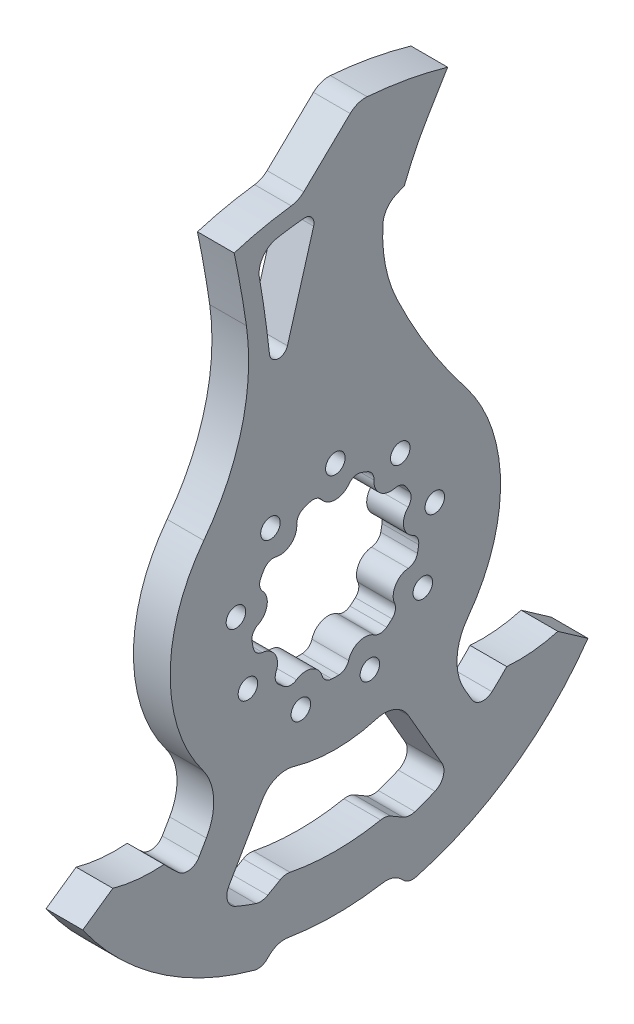
SolidWorks part; units mm, degrees
material "AR500"
ref_plane "Front Plane" through (0, 0, 0) normal (0, 0, 1) x (1, 0, 0)
ref_plane "Top Plane" through (0, 0, 0) normal (0, 1, 0) x (1, 0, 0)
ref_plane "Right Plane" through (0, 0, 0) normal (1, 0, 0) x (0, 0, -1)
other "Center of Mass"
sketch "Sketch1" plane through (0, 0, 0) normal (1, 0, 0) x (0, 0, -1)
  circle A0 centre (0, 0) radius 139.7 construction
  circle A1 centre (0, 0) radius 106.68 construction
  circle A2 centre (0, 0) radius 44.45 construction
  dimension "D1" = 279.4
  dimension "D2" = 33.02
  dimension "D3" = 88.9
sketch "Sketch2" plane through (0, 0, 0) normal (1, 0, 0) x (0, 0, -1)
  line L0 (0, 0) -> (38.858, 134.187) construction
  line L1 (38.858, 134.187) -> (32.2885, 123.3181)
  line L2 (0, 0) -> (0, 61.679) construction
  line L3 (7.5549, 139.4956) -> (-12.768, 119.9725)
  line L4 (-35.0051, 115.4602) -> (-40.3483, 140.8902) construction
  line L5 (23.88, 106.192) -> (20.1469, 96.5425) construction
  line L6 (23.88, 106.192) -> (16.9106, 103.1109)
  line L7 (16.9106, 103.1109) -> (16.6566, 100.7528)
  line L8 (-35.0051, 115.4602) -> (-4.6687, 124.6576) construction
  line L10 (0, -100.33) -> (0, 0) construction
  line L11 (-20.0866, -98.2987) -> (-25.4, -103.6121)
  line L16 (-49.9001, -64.1593) -> (-37.6706, -42.9773)
  line L17 (87.3871, -61.1891) -> (76.9839, -53.9047)
  line L18 (-87.3871, -61.1891) -> (-76.9839, -53.9047)
  line L19 (49.9001, -64.1593) -> (37.6706, -42.9773)
  line L24 (53.8815, -53.8815) -> (0, 0) construction
  line L25 (20.0866, -98.2987) -> (25.4, -103.6121)
  circle A0 centre (0, 0) radius 139.7 construction
  arc A1 (38.858, 134.187) -> (7.5549, 139.4956) centre (0, 0) ccw
  arc A2 (-12.768, 119.9725) -> (-35.0051, 115.4602) centre (0, 0) ccw
  arc A3 (32.2885, 123.3181) -> (23.88, 106.192) centre (125.9607, 66.6999) ccw
  arc A4 (44.9569, 35.2845) -> (37.6706, -42.9773) centre (0, 0) cw
  circle A5 centre (0, 0) radius 44.45 construction
  arc A6 (21.2843, 73.5004) -> (16.6566, 100.7528) centre (67.1642, 95.3105) cw
  arc A7 (-35.0051, 115.4602) -> (-30.7712, 91.5455) centre (-407.8633, 37.1165) cw
  arc A8 (-30.7712, 91.5455) -> (-45.5098, 34.5685) centre (-106.1896, 80.6597) cw
  arc A9 (-45.5098, 34.5685) -> (-37.6706, -42.9773) centre (0, 0) ccw
  arc A10 (-87.3871, -61.1891) -> (-25.4, -103.6121) centre (0, 0) ccw
  circle A11 centre (0, 0) radius 106.68 construction
  arc A18 (-76.9839, -53.9047) -> (-59.2852, -55.6031) centre (-63.357, -4.9665) ccw
  arc A19 (-59.2852, -55.6031) -> (-49.9001, -64.1593) centre (0, 0) ccw
  arc A20 (-20.0866, -98.2987) -> (20.0866, -98.2987) centre (0, 0) ccw
  arc A21 (59.2852, -55.6031) -> (49.9001, -64.1593) centre (0, 0) cw
  arc A22 (76.9839, -53.9047) -> (59.2852, -55.6031) centre (63.357, -4.9665) cw
  arc A23 (87.3871, -61.1891) -> (25.4, -103.6121) centre (0, 0) cw
  circle A24 centre (0, 0) radius 44.45
  arc A25 (21.2843, 73.5004) -> (44.9569, 35.2845) centre (204.8038, 160.7405) ccw
  dimension "D4" = 19.05
  dimension "D11" = 57.15
  dimension "D13" = 50.8
  dimension "D14" = 381
  dimension "D16" = 76.2
  dimension "D19" = 6.35
  dimension "D21" = 55
  dimension "D26" = 17.78
  dimension "D22" = 25.4
  dimension "D23" = 50.8
  dimension "D27" = 12.7
  dimension "D29" = 203.2
  dimension "D1" = 15
  dimension "D2" = 16.15
  dimension "D3" = 15
  dimension "D5" = 31.75
  dimension "D6" = 12.7
  dimension "D7" = 31.75
  dimension "D8" = 5
  dimension "D9" = 45
  dimension "D10" = 10
  dimension "D12" = 7.62
  dimension "D15" = 85
  dimension "D17" = 76.2
  dimension "D18" = 25.4
  dimension "D20" = 45
  dimension "D24" = 12.7
  dimension "D25" = 45
  dimension "D28" = 30
extrude "Boss-Extrude1" add sketch "Sketch2" along normal mid plane 12.7
sketch "Sketch3" plane through (6.35, 0, 0) normal (1, 0, 0) x (0, 0, -1)
  line L1 (-7.513, 109.7387) -> (-16.5762, 78.441)
  line L2 (16.6566, 100.7528) -> (16.9106, 103.1109) construction
  line L3 (-3.2803, 66.3447) -> (4.4504, 105.5668) construction
  line L4 (16.9106, 103.1109) -> (-8.0099, 108.0227) construction
  arc A0 (-12.768, 119.9725) -> (-35.0051, 115.4602) centre (0, 0) ccw construction
  arc A1 (-30.7712, 91.5455) -> (-35.0051, 115.4602) centre (-407.8633, 37.1165) ccw construction
  arc A2 (-7.513, 109.7387) -> (-10.8645, 113.7825) centre (-10.5627, 110.6219) ccw
  arc A3 (-12.768, 119.9725) -> (-35.0051, 115.4602) centre (0, 0) ccw construction
  arc A4 (-30.7712, 91.5455) -> (-35.0051, 115.4602) centre (-407.8633, 37.1165) ccw construction
  arc A5 (-10.8645, 113.7825) -> (-27.6085, 110.9156) centre (0, 0) ccw
  arc A6 (-22.7823, 78.981) -> (-27.6085, 110.9156) centre (-407.8633, 37.1165) ccw
  arc A7 (-24.4863, 92.4527) -> (-27.6085, 110.9156) centre (-407.8633, 37.1165) ccw construction
  arc A8 (-12.096, 113.6582) -> (-27.6085, 110.9156) centre (0, 0) ccw construction
  arc A14 (-22.7823, 78.981) -> (-16.5762, 78.441) centre (-19.6259, 79.3242) ccw
  point P18 (16.9106, 103.1109)
  dimension "D5" = 3.175
  dimension "D7" = 3.175
  dimension "D3" = 10
  dimension "D4" = 25.4
  dimension "D1" = 6.35
extrude "Cut-Extrude1" cut sketch "Sketch3" against normal through all
fillet "Fillet1" radius 7.62 6 edges at (0, 103.1109, -16.9106) (0, 110.9156, 27.6085) (0, 139.4956, -7.5549) (0, 119.9725, 12.768) (0, -98.2987, -20.0866) (0, -98.2987, 20.0866)
fillet "Fillet4" radius 19.05 2 edges at (0, -42.9773, -37.6706) (0, -42.9773, 37.6706)
fillet "Fillet2" radius 4.572 4 edges at (0, -103.6121, 25.4) (0, -103.6121, -25.4) (0, -64.1593, -49.9001) (0, -64.1593, 49.9001)
sketch "Sketch4" plane through (6.35, 0, 0) normal (1, 0, 0) x (0, 0, -1)
  line L0 (-21.1843, -46.1721) -> (-39.646, -78.1487)
  line L1 (-44.6265, -55.0252) -> (-47.1846, -59.4559) construction
  line L2 (0, -81.28) -> (0, -50.8)
  line L3 (-25.3274, -83.8901) -> (-17.5035, -79.373)
  line L4 (-11.6185, -94.3061) -> (-25.8749, -102.5371) construction
  arc A0 (-39.646, -78.1487) -> (-25.3274, -83.8901) centre (0, 0) ccw
  arc A1 (0, -50.8) -> (-21.1843, -46.1721) centre (0, 0) cw
  circle A2 centre (0, 0) radius 44.45 construction
  circle A3 centre (0, 0) radius 106.68 construction
  arc A4 (-17.5035, -79.373) -> (0, -81.28) centre (0, 0) ccw
  arc A5 (-16.2916, -98.9984) -> (16.2916, -98.9984) centre (0, 0) ccw construction
  arc A6 (-87.3871, -61.1891) -> (-27.9851, -102.9439) centre (0, 0) ccw construction
  arc A7 (-16.2916, -98.9984) -> (-22.9171, -101.1292) centre (-17.5289, -106.5173) ccw construction
  dimension "D1" = 50.8
  dimension "D3" = 19.05
  dimension "D4" = 19.05
  dimension "D2" = 15.875
  dimension "D5" = 30
  dimension "D6" = 15.875
extrude "Cut-Extrude2" cut sketch "Sketch4" against normal through all
mirror "Mirror1" about plane through (-6.35, -81.28, 0) normal (0, 0, -1) of "Cut-Extrude2"
fillet "Fillet3" radius 5.08 6 edges at (0, -78.1487, -39.646) (0, -83.8901, -25.3274) (0, -79.373, -17.5035) (0, -79.373, 17.5035) (0, -83.8901, 25.3274) (0, -78.1487, 39.646)
fillet "Fillet5" radius 9.525 2 edges at (0, -46.1721, -21.1843) (0, -46.1721, 21.1843)
ref_axis "Axis1" through (6.35, 0, 0) along (-1, 0, 0)
sketch "Sketch5" plane through (-6.35, 0, 0) normal (-1, 0, 0) x (0, 0, 1)
  arc A36 (-24.1266, 15.3113) -> (-25.3233, 13.2386) centre (0, 0) ccw construction
  arc A37 (-20.6919, 16.6942) -> (-24.1266, 15.3113) centre (-21.4459, 13.6101) ccw construction
  arc A38 (-20.6919, 16.6942) -> (-12.8475, 23.2765) centre (-19.184, 22.8626) ccw construction
  arc A39 (-10.8892, 26.4189) -> (-12.8475, 23.2765) centre (-9.6793, 23.4834) ccw construction
  arc A40 (-8.6401, 27.2374) -> (-10.8892, 26.4189) centre (0, 0) ccw construction
  arc A41 (-5.1201, 26.089) -> (-8.6401, 27.2374) centre (-7.6801, 24.2111) ccw construction
  arc A42 (-5.1201, 26.089) -> (5.1201, 26.089) centre (0, 29.845) ccw construction
  arc A43 (8.6401, 27.2374) -> (5.1201, 26.089) centre (7.6801, 24.2111) ccw construction
  arc A44 (10.8892, 26.4189) -> (8.6401, 27.2374) centre (0, 0) ccw construction
  arc A45 (12.8475, 23.2765) -> (10.8892, 26.4189) centre (9.6793, 23.4834) ccw construction
  arc A46 (12.8475, 23.2765) -> (20.6919, 16.6942) centre (19.184, 22.8626) ccw construction
  arc A47 (24.1266, 15.3113) -> (20.6919, 16.6942) centre (21.4459, 13.6101) ccw construction
  arc A48 (25.3233, 13.2386) -> (24.1266, 15.3113) centre (0, 0) ccw construction
  arc A49 (24.8036, 9.5726) -> (25.3233, 13.2386) centre (22.5096, 11.7677) ccw construction
  arc A50 (24.8036, 9.5726) -> (26.5818, -0.512) centre (29.3916, 5.1825) ccw construction
  arc A51 (28.324, -3.7791) -> (26.5818, -0.512) centre (25.1769, -3.3592) ccw construction
  arc A52 (27.9084, -6.1361) -> (28.324, -3.7791) centre (0, 0) ccw construction
  arc A53 (25.1538, -8.6104) -> (27.9084, -6.1361) centre (24.8075, -5.4543) ccw construction
  arc A54 (25.1538, -8.6104) -> (20.0337, -17.4786) centre (25.8465, -14.9225) ccw construction
  arc A55 (19.2682, -21.1013) -> (20.0337, -17.4786) centre (17.1273, -18.7567) ccw construction
  arc A56 (17.4348, -22.6397) -> (19.2682, -21.1013) centre (0, 0) ccw construction
  arc A57 (13.7343, -22.7645) -> (17.4348, -22.6397) centre (15.4976, -20.1242) ccw construction
  arc A58 (13.7343, -22.7645) -> (4.1117, -26.2669) centre (10.2076, -28.0451) ccw construction
  arc A59 (1.1967, -28.5499) -> (4.1117, -26.2669) centre (1.0637, -25.3777) ccw construction
  arc A60 (-1.1967, -28.5499) -> (1.1967, -28.5499) centre (0, 0) ccw construction
  arc A61 (-4.1117, -26.2669) -> (-1.1967, -28.5499) centre (-1.0637, -25.3777) ccw construction
  arc A62 (-4.1117, -26.2669) -> (-13.7343, -22.7645) centre (-10.2076, -28.0451) ccw construction
  arc A63 (-17.4348, -22.6397) -> (-13.7343, -22.7645) centre (-15.4976, -20.1242) ccw construction
  arc A64 (-19.2682, -21.1013) -> (-17.4348, -22.6397) centre (0, 0) ccw construction
  arc A65 (-20.0337, -17.4786) -> (-19.2682, -21.1013) centre (-17.1273, -18.7567) ccw construction
  arc A66 (-20.0337, -17.4786) -> (-25.1538, -8.6104) centre (-25.8465, -14.9225) ccw construction
  arc A67 (-27.9084, -6.1361) -> (-25.1538, -8.6104) centre (-24.8075, -5.4543) ccw construction
  arc A68 (-28.324, -3.7791) -> (-27.9084, -6.1361) centre (0, 0) ccw construction
  arc A69 (-26.5818, -0.512) -> (-28.324, -3.7791) centre (-25.1769, -3.3592) ccw construction
  arc A70 (-26.5818, -0.512) -> (-24.8036, 9.5726) centre (-29.3916, 5.1825) ccw construction
  arc A71 (-25.3233, 13.2386) -> (-24.8036, 9.5726) centre (-22.5096, 11.7677) ccw construction
  circle A108 centre (0, 0) radius 44.45 construction
  circle A109 centre (0, 0) radius 44.45
  arc A146 (-24.1266, 15.3113) -> (-25.3233, 13.2386) centre (0, 0) ccw construction
  arc A147 (-20.6919, 16.6942) -> (-24.1266, 15.3113) centre (-21.4459, 13.6101) ccw construction
  arc A148 (-20.6919, 16.6942) -> (-12.8475, 23.2765) centre (-19.184, 22.8626) ccw construction
  arc A149 (-10.8892, 26.4189) -> (-12.8475, 23.2765) centre (-9.6793, 23.4834) ccw construction
  arc A150 (-8.6401, 27.2374) -> (-10.8892, 26.4189) centre (0, 0) ccw construction
  arc A151 (-5.1201, 26.089) -> (-8.6401, 27.2374) centre (-7.6801, 24.2111) ccw construction
  arc A152 (-5.1201, 26.089) -> (5.1201, 26.089) centre (0, 29.845) ccw construction
  arc A153 (8.6401, 27.2374) -> (5.1201, 26.089) centre (7.6801, 24.2111) ccw construction
  arc A154 (10.8892, 26.4189) -> (8.6401, 27.2374) centre (0, 0) ccw construction
  arc A155 (12.8475, 23.2765) -> (10.8892, 26.4189) centre (9.6793, 23.4834) ccw construction
  arc A156 (12.8475, 23.2765) -> (20.6919, 16.6942) centre (19.184, 22.8626) ccw construction
  arc A157 (24.1266, 15.3113) -> (20.6919, 16.6942) centre (21.4459, 13.6101) ccw construction
  arc A158 (25.3233, 13.2386) -> (24.1266, 15.3113) centre (0, 0) ccw construction
  arc A159 (24.8036, 9.5726) -> (25.3233, 13.2386) centre (22.5096, 11.7677) ccw construction
  arc A160 (24.8036, 9.5726) -> (26.5818, -0.512) centre (29.3916, 5.1825) ccw construction
  arc A161 (28.324, -3.7791) -> (26.5818, -0.512) centre (25.1769, -3.3592) ccw construction
  arc A162 (27.9084, -6.1361) -> (28.324, -3.7791) centre (0, 0) ccw construction
  arc A163 (25.1538, -8.6104) -> (27.9084, -6.1361) centre (24.8075, -5.4543) ccw construction
  arc A164 (25.1538, -8.6104) -> (20.0337, -17.4786) centre (25.8465, -14.9225) ccw construction
  arc A165 (19.2682, -21.1013) -> (20.0337, -17.4786) centre (17.1273, -18.7567) ccw construction
  arc A166 (17.4348, -22.6397) -> (19.2682, -21.1013) centre (0, 0) ccw construction
  arc A167 (13.7343, -22.7645) -> (17.4348, -22.6397) centre (15.4976, -20.1242) ccw construction
  arc A168 (13.7343, -22.7645) -> (4.1117, -26.2669) centre (10.2076, -28.0451) ccw construction
  arc A169 (1.1967, -28.5499) -> (4.1117, -26.2669) centre (1.0637, -25.3777) ccw construction
  arc A170 (-1.1967, -28.5499) -> (1.1967, -28.5499) centre (0, 0) ccw construction
  arc A171 (-4.1117, -26.2669) -> (-1.1967, -28.5499) centre (-1.0637, -25.3777) ccw construction
  arc A172 (-4.1117, -26.2669) -> (-13.7343, -22.7645) centre (-10.2076, -28.0451) ccw construction
  arc A173 (-17.4348, -22.6397) -> (-13.7343, -22.7645) centre (-15.4976, -20.1242) ccw construction
  arc A174 (-19.2682, -21.1013) -> (-17.4348, -22.6397) centre (0, 0) ccw construction
  arc A175 (-20.0337, -17.4786) -> (-19.2682, -21.1013) centre (-17.1273, -18.7567) ccw construction
  arc A176 (-20.0337, -17.4786) -> (-25.1538, -8.6104) centre (-25.8465, -14.9225) ccw construction
  arc A177 (-27.9084, -6.1361) -> (-25.1538, -8.6104) centre (-24.8075, -5.4543) ccw construction
  arc A178 (-28.324, -3.7791) -> (-27.9084, -6.1361) centre (0, 0) ccw construction
  arc A179 (-26.5818, -0.512) -> (-28.324, -3.7791) centre (-25.1769, -3.3592) ccw construction
  arc A180 (-26.5818, -0.512) -> (-24.8036, 9.5726) centre (-29.3916, 5.1825) ccw construction
  arc A181 (-25.3233, 13.2386) -> (-24.8036, 9.5726) centre (-22.5096, 11.7677) ccw construction
  arc A182 (-24.5555, 15.5835) -> (-25.7735, 13.474) centre (0, 0) ccw
  arc A183 (-25.7735, 13.474) -> (-25.1706, 9.2214) centre (-22.5096, 11.7677) ccw
  arc A184 (-26.8066, -0.0564) -> (-25.1706, 9.2214) centre (-29.3916, 5.1825) ccw
  arc A185 (-26.8066, -0.0564) -> (-28.8275, -3.8463) centre (-25.1769, -3.3592) ccw
  arc A186 (-28.8275, -3.8463) -> (-28.4045, -6.2452) centre (0, 0) ccw
  arc A187 (-28.4045, -6.2452) -> (-25.2092, -9.1154) centre (-24.8075, -5.4543) ccw
  arc A188 (-20.4988, -17.2742) -> (-25.2092, -9.1154) centre (-25.8465, -14.9225) ccw
  arc A189 (-20.4988, -17.2742) -> (-19.6108, -21.4764) centre (-17.1273, -18.7567) ccw
  arc A190 (-19.6108, -21.4764) -> (-17.7448, -23.0422) centre (0, 0) ccw
  arc A191 (-17.7448, -23.0422) -> (-13.4521, -23.187) centre (-15.4976, -20.1242) ccw
  arc A192 (-4.5993, -26.4091) -> (-13.4521, -23.187) centre (-10.2076, -28.0451) ccw
  arc A193 (-4.5993, -26.4091) -> (-1.2179, -29.0575) centre (-1.0637, -25.3777) ccw
  arc A194 (-1.2179, -29.0575) -> (1.2179, -29.0575) centre (0, 0) ccw
  arc A195 (1.2179, -29.0575) -> (4.5993, -26.4091) centre (1.0637, -25.3777) ccw
  arc A196 (13.4521, -23.187) -> (4.5993, -26.4091) centre (10.2076, -28.0451) ccw
  arc A197 (13.4521, -23.187) -> (17.7448, -23.0422) centre (15.4976, -20.1242) ccw
  arc A198 (17.7448, -23.0422) -> (19.6108, -21.4764) centre (0, 0) ccw
  arc A199 (19.6108, -21.4764) -> (20.4988, -17.2742) centre (17.1273, -18.7567) ccw
  arc A200 (25.2092, -9.1154) -> (20.4988, -17.2742) centre (25.8465, -14.9225) ccw
  arc A201 (25.2092, -9.1154) -> (28.4045, -6.2452) centre (24.8075, -5.4543) ccw
  arc A202 (28.4045, -6.2452) -> (28.8275, -3.8463) centre (0, 0) ccw
  arc A203 (28.8275, -3.8463) -> (26.8066, -0.0564) centre (25.1769, -3.3592) ccw
  arc A204 (25.1706, 9.2214) -> (26.8066, -0.0564) centre (29.3916, 5.1825) ccw
  arc A205 (25.1706, 9.2214) -> (25.7735, 13.474) centre (22.5096, 11.7677) ccw
  arc A206 (25.7735, 13.474) -> (24.5555, 15.5835) centre (0, 0) ccw
  arc A207 (24.5555, 15.5835) -> (20.5713, 17.1877) centre (21.4459, 13.6101) ccw
  arc A208 (13.3544, 23.2434) -> (20.5713, 17.1877) centre (19.184, 22.8626) ccw
  arc A209 (13.3544, 23.2434) -> (11.0827, 26.8885) centre (9.6793, 23.4834) ccw
  arc A210 (11.0827, 26.8885) -> (8.7937, 27.7217) centre (0, 0) ccw
  arc A211 (8.7937, 27.7217) -> (4.7105, 26.3895) centre (7.6801, 24.2111) ccw
  arc A212 (-4.7105, 26.3895) -> (4.7105, 26.3895) centre (0, 29.845) ccw
  arc A213 (-4.7105, 26.3895) -> (-8.7937, 27.7217) centre (-7.6801, 24.2111) ccw
  arc A214 (-8.7937, 27.7217) -> (-11.0827, 26.8885) centre (0, 0) ccw
  arc A215 (-11.0827, 26.8885) -> (-13.3544, 23.2434) centre (-9.6793, 23.4834) ccw
  arc A216 (-20.5713, 17.1877) -> (-13.3544, 23.2434) centre (-19.184, 22.8626) ccw
  arc A217 (-20.5713, 17.1877) -> (-24.5555, 15.5835) centre (-21.4459, 13.6101) ccw
  dimension "D1" = 0.508
extrude "Boss-Extrude2" add sketch "Sketch5" against normal up to surface (12.7 mm away) up to face at (6.35, 99.483, 17.4857)
hole_wizard "1/4 Clearance Hole1" positions "Sketch6" profile "Sketch8" hole size "1/4" standard "ANSI Inch" end condition through all
sketch "Sketch6" plane through (6.35, 0, 0) normal (1, 0, 0) x (0, 0, -1)
  point P0 (0, 34.925)
sketch "Sketch8" plane through (6.35, 34.925, 0) normal (0, 1, 0) x (0, 0, -1)
  line L0 (0, 0) -> (0, 12.7)
  line L1 (0, 12.7) -> (3.3782, 12.7)
  line L2 (3.3782, 12.7) -> (3.3782, 0)
  line L5 (3.3782, 0) -> (0, 0)
  line L11 (0, -6.35) -> (0, 107.95) construction
  dimension "Thru Hole Dia." = 6.7564
  dimension "Thru Hole Depth" = 12.7
pattern_circular "CirPattern1" count 9 over 360 about axis through (6.35, 0, 0) along (-1, 0, 0) of "1/4 Clearance Hole1"
